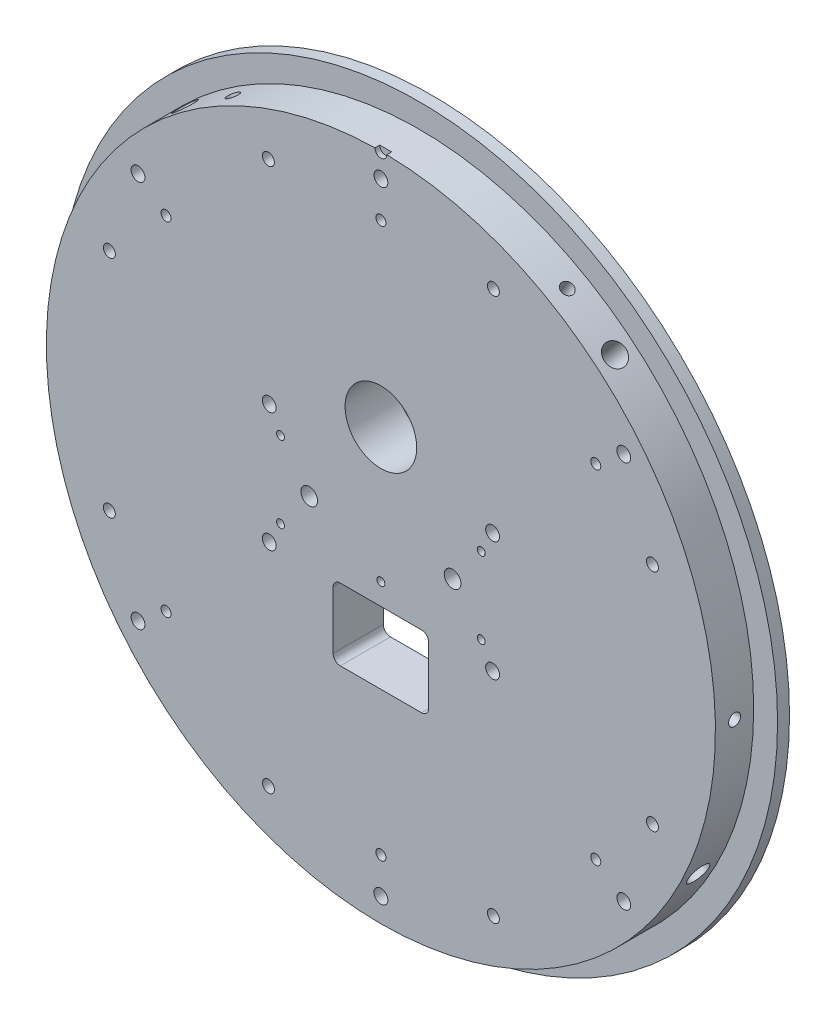
SolidWorks part; units mm, degrees
material "2017-T4"
ref_plane "正面" through (0, 0, 0) normal (0, 0, 1) x (1, 0, 0)
ref_plane "平面" through (0, 0, 0) normal (0, 1, 0) x (1, 0, 0)
ref_plane "右側面" through (0, 0, 0) normal (1, 0, 0) x (0, 0, -1)
ref_axis "中心軸" through (0, 0, -1.05) along (0, 0, 1)
sketch "ｽｹｯﾁ1" plane through (0, 0, 0) normal (0, 0, 1) x (1, 0, 0)
  circle A0 centre (0, 0) radius 150
  dimension "D1" = 300
extrude "ﾎﾞｽ - 押し出し1" add sketch "ｽｹｯﾁ1" along normal blind 5
sketch "ｽｹｯﾁ2" plane through (0, 0, 5) normal (0, 0, 1) x (1, 0, 0)
  circle A0 centre (0, 0) radius 140
  dimension "D1" = 280
extrude "ﾎﾞｽ - 押し出し2" add sketch "ｽｹｯﾁ2" along normal blind 16 contours A0
sketch "ｽｹｯﾁ3" plane through (0, 0, 0) normal (0, 0, -1) x (-1, 0, 0)
  line L1 (-20, -55) -> (20, -55)
  line L2 (-20, -55) -> (-20, -25)
  line L3 (-20, -25) -> (20, -25)
  line L4 (20, -55) -> (20, -25)
  line L5 (-20, -55) -> (20, -25) construction
  line L6 (-20, -25) -> (20, -55) construction
  circle A0 centre (0, 40) radius 15
  point P2 (0, -40)
  dimension "D1" = 30
  dimension "D2" = 40
  dimension "D3" = 40
  dimension "D4" = 30
  dimension "D5" = 55
extrude "ｶｯﾄ - 押し出し1" cut sketch "ｽｹｯﾁ3" against normal through all
fillet "ﾌｨﾚｯﾄ2" radius 3 4 edges at (20, -55, 10.5) (20, -25, 10.5) (-20, -25, 10.5) (-20, -55, 10.5)
sketch "ｽｹｯﾁ5" plane through (0, 0, 0) normal (0, 0, -1) x (-1, 0, 0)
  circle A0 centre (0, 0) radius 130
  point P3 (0, 130)
  point P4 (101.6401, 81.0511)
  point P5 (-101.6401, 81.0511)
  point P6 (-101.6401, -81.0511)
  point P7 (101.6401, -81.0511)
  point P8 (0, -130)
  dimension "D1" = 260
  dimension "D2" = 51.43
  dimension "D3" = 51.43
  dimension "D4" = 51.43
  dimension "D5" = 51.43
hole_wizard "M5 穴付きねじ用座ぐり穴1" positions "3Dｽｹｯﾁ1" profile "ｽｹｯﾁ4" counterbore size "M5" standard "JIS" end condition through all
sketch3d "3Dｽｹｯﾁ1"
  point P0 (0, 130, 0)
  point P2 (-101.6401, 81.0511, 0)
  point P4 (101.6401, 81.0511, 0)
  point P6 (101.6401, -81.0511, 0)
  point P8 (0, -130, 0)
  point P10 (-101.6401, -81.0511, 0)
sketch "ｽｹｯﾁ4" plane through (0, 130, 0) normal (1, 0, 0) x (0, 1, 0)
  line L0 (0, 0) -> (0, 21)
  line L1 (0, 21) -> (2.9, 21)
  line L3 (2.9, 21) -> (2.9, 8)
  line L4 (2.9, 8) -> (5, 8)
  line L5 (5, 8) -> (5, 0)
  line L7 (5, 0) -> (0, 0)
  line L11 (0, -6.35) -> (0, 107.95) construction
  dimension "通し穴の直径" = 5.8
  dimension "通し穴の深さ" = 21
  dimension "座ぐり穴の直径" = 10
  dimension "座ぐり穴の深さ" = 8
sketch "ｽｹｯﾁ7" plane through (0, 0, 0) normal (0, 0, -1) x (-1, 0, 0)
  point P0 (-30, 0)
  point P1 (30, 0)
  dimension "D1" = 30
  dimension "D2" = 30
hole_wizard "M6 穴付きねじ用座ぐり穴1" positions "3Dｽｹｯﾁ2" profile "ｽｹｯﾁ6" counterbore size "M6" standard "JIS" end condition through all
sketch3d "3Dｽｹｯﾁ2"
  point P0 (30, 0, 0)
  point P2 (-30, 0, 0)
sketch "ｽｹｯﾁ6" plane through (30, 0, 0) normal (1, 0, 0) x (0, 1, 0)
  line L0 (0, 0) -> (0, 21)
  line L1 (0, 21) -> (3.5, 21)
  line L3 (3.5, 21) -> (3.5, 9)
  line L4 (3.5, 9) -> (5.5, 9)
  line L5 (5.5, 9) -> (5.5, 0)
  line L7 (5.5, 0) -> (0, 0)
  line L11 (0, -6.35) -> (0, 107.95) construction
  dimension "通し穴の直径" = 7
  dimension "通し穴の深さ" = 21
  dimension "座ぐり穴の直径" = 11
  dimension "座ぐり穴の深さ" = 9
sketch "ｽｹｯﾁ8" plane through (0, 0, 0) normal (0, 0, -1) x (-1, 0, 0)
  line L1 (-46.7333, -25) -> (46.7333, -25) construction
  line L2 (-46.7333, -25) -> (-46.7333, 25) construction
  line L3 (-46.7333, 25) -> (46.7333, 25) construction
  line L4 (46.7333, -25) -> (46.7333, 25) construction
  line L5 (-46.7333, -25) -> (46.7333, 25) construction
  line L6 (-46.7333, 25) -> (46.7333, -25) construction
  point P0 (0, 0)
  dimension "D1" = 50
  dimension "D2" = 53
hole_wizard "M5 穴付きねじ用座ぐり穴2" positions "3Dｽｹｯﾁ3" profile "ｽｹｯﾁ9" counterbore size "M5" standard "JIS" end condition through all
sketch3d "3Dｽｹｯﾁ3"
  point P0 (46.7333, 25, 0)
  point P3 (46.7333, -25, 0)
  point P6 (-46.7333, 25, 0)
  point P9 (-46.7333, -25, 0)
sketch "ｽｹｯﾁ9" plane through (46.7333, 25, 0) normal (1, 0, 0) x (0, 1, 0)
  line L0 (0, 0) -> (0, 21)
  line L1 (0, 21) -> (2.9, 21)
  line L3 (2.9, 21) -> (2.9, 8)
  line L4 (2.9, 8) -> (5, 8)
  line L5 (5, 8) -> (5, 0)
  line L7 (5, 0) -> (0, 0)
  line L11 (0, -6.35) -> (0, 107.95) construction
  dimension "通し穴の直径" = 5.8
  dimension "通し穴の深さ" = 21
  dimension "座ぐり穴の直径" = 10
  dimension "座ぐり穴の深さ" = 8
sketch "ｽｹｯﾁ10" plane through (0, 0, 0) normal (0, 0, -1) x (-1, 0, 0)
  line L1 (-42, -16) -> (42, -16)
  line L2 (-42, -16) -> (-42, 16)
  line L3 (-42, 16) -> (42, 16)
  line L4 (42, -16) -> (42, 16)
  line L5 (-42, -16) -> (42, 16) construction
  line L6 (-42, 16) -> (42, -16) construction
  point P0 (0, 0)
  point P5 (0, -16)
  dimension "D1" = 84
  dimension "D2" = 32
hole_wizard "M4x0.7 ねじ穴1" positions "3Dｽｹｯﾁ4" profile "ｽｹｯﾁ11" tap size "M4x0.7" standard "JIS" end condition through all
sketch3d "3Dｽｹｯﾁ4"
  point P0 (42, 16, 0)
  point P3 (-42, 16, 0)
  point P6 (-42, -16, 0)
  point P9 (0, -16, 0)
  point P12 (42, -16, 0)
sketch "ｽｹｯﾁ11" plane through (42, 16, 0) normal (1, 0, 0) x (0, 1, 0)
  line L0 (0, 0) -> (0, 21)
  line L1 (0, 21) -> (1.65, 21)
  line L2 (1.65, 21) -> (1.65, 0)
  line L5 (1.65, 0) -> (0, 0)
  line L11 (0, -6.35) -> (0, 107.95) construction
  dimension "次ｻｰﾌｪｽまでのねじ下穴ﾄﾞﾘﾙ直径" = 3.3
  dimension "次ｻｰﾌｪｽまでのねじ下穴ﾄﾞﾘﾙの深さ" = 21
cosmetic thread "穴のねじ山1" parameters "D2"=4
cosmetic thread "穴のねじ山2" parameters "D2"=4
cosmetic thread "穴のねじ山3" parameters "D2"=4
cosmetic thread "穴のねじ山4" parameters "D2"=4
cosmetic thread "穴のねじ山5" parameters "D2"=4
sketch "ｽｹｯﾁ12" plane through (0, 0, 0) normal (0, 0, -1) x (-1, 0, 0)
  line L0 (0, 0) -> (212.6109, 0) construction
  line L1 (0, 0) -> (198.3068, 82.1414) construction
  point P3 (113.6372, 47.0701)
  dimension "D1" = 123
  dimension "D2" = 22.5
hole_wizard "M6x1.0 ねじ穴1" positions "3Dｽｹｯﾁ5" profile "ｽｹｯﾁ13" tap size "M6x1.0" standard "JIS" end condition through all
sketch3d "3Dｽｹｯﾁ5"
  point P0 (-113.6372, 47.0701, 0)
sketch "ｽｹｯﾁ13" plane through (-113.6372, 47.0701, 0) normal (1, 0, 0) x (0, 1, 0)
  line L0 (0, 0) -> (0, 21)
  line L1 (0, 21) -> (2.5, 21)
  line L2 (2.5, 21) -> (2.5, 0)
  line L5 (2.5, 0) -> (0, 0)
  line L11 (0, -6.35) -> (0, 107.95) construction
  dimension "次ｻｰﾌｪｽまでのねじ下穴ﾄﾞﾘﾙ直径" = 5
  dimension "次ｻｰﾌｪｽまでのねじ下穴ﾄﾞﾘﾙの深さ" = 21
cosmetic thread "穴のねじ山6" parameters "D2"=6
pattern_circular "円形ﾊﾟﾀｰﾝ1" count 8 over 360 about axis through (0, 0, -1.05) along (0, 0, 1) of "M6x1.0 ねじ穴1"
sketch "ｽｹｯﾁ14" plane through (0, 0, 21) normal (0, 0, -1) x (-1, 0, 0)
  circle A0 centre (0, 140) radius 2.5
  circle A2 centre (0, 0) radius 140 construction
  dimension "D1" = 5
extrude "ｶｯﾄ - 押し出し2" cut sketch "ｽｹｯﾁ14" along normal blind 2
sketch "ｽｹｯﾁ16" plane through (0, 0, 0) normal (0, 0, 1) x (1, 0, 0)
  circle A0 centre (0, 0) radius 115
  point P3 (0, 115)
  point P4 (89.9124, 71.6991)
  point P5 (-89.9124, 71.6991)
  point P6 (-89.9124, -71.6991)
  point P7 (89.9124, -71.6991)
  point P8 (0, -115)
  dimension "D1" = 230
  dimension "D2" = 51.43
  dimension "D3" = 51.43
  dimension "D4" = 51.43
  dimension "D5" = 51.43
hole_wizard "M5x0.8 ねじ穴1" positions "3Dｽｹｯﾁ6" profile "ｽｹｯﾁ17" tap size "M5x0.8" standard "JIS" end condition through all
sketch3d "3Dｽｹｯﾁ6"
  point P0 (-89.9124, 71.6991, 0)
  point P3 (-89.9124, 71.6991, 0)
  point P5 (-89.9124, -71.6991, 0)
  point P7 (0, -115, 0)
  point P9 (89.9124, -71.6991, 0)
  point P11 (89.9124, 71.6991, 0)
  point P13 (0, 115, 0)
sketch "ｽｹｯﾁ17" plane through (-89.9124, 71.6991, 0) normal (1, 0, 0) x (0, 1, 0)
  line L0 (0, 0) -> (0, 21)
  line L1 (0, 21) -> (2.1, 21)
  line L2 (2.1, 21) -> (2.1, 0)
  line L5 (2.1, 0) -> (0, 0)
  line L11 (0, -6.35) -> (0, 107.95) construction
  dimension "次ｻｰﾌｪｽまでのねじ下穴ﾄﾞﾘﾙ直径" = 4.2
  dimension "次ｻｰﾌｪｽまでのねじ下穴ﾄﾞﾘﾙの深さ" = 21
cosmetic thread "穴のねじ山7" parameters "D2"=5
cosmetic thread "穴のねじ山8" parameters "D2"=5
cosmetic thread "穴のねじ山9" parameters "D2"=5
cosmetic thread "穴のねじ山10" parameters "D2"=5
cosmetic thread "穴のねじ山11" parameters "D2"=5
cosmetic thread "穴のねじ山12" parameters "D2"=5
cosmetic thread "穴のねじ山13" parameters "D2"=5
ref_plane "平面1" through (0, 0, 13) normal (0, 0, 1) x (1, 0, 0)
sketch "ｽｹｯﾁ18" plane through (0, 0, 13) normal (0, 0, 1) x (1, 0, 0)
  circle A0 centre (0, 0) radius 140 construction
  circle A1 centre (0, 0) radius 140 construction
  point P0 (140, 0)
hole_wizard "M6x1.0 ねじ穴2" positions "3Dｽｹｯﾁ7" profile "ｽｹｯﾁ19" tap size "M6x1.0" standard "JIS"
sketch3d "3Dｽｹｯﾁ7"
  point P0 (140, 0, 13)
sketch "ｽｹｯﾁ19" plane through (140, 0, 13) normal (0, 1, 0) x (0, 0, -1)
  line L0 (0, 0) -> (0, 21.5022)
  line L1 (0, 21.5022) -> (2.5, 20)
  line L2 (2.5, 20) -> (2.5, 0)
  line L5 (2.5, 0) -> (0, 0)
  line L10 (0, 21.5022) -> (-2.5, 20) construction
  line L11 (0, -6.35) -> (0, 107.95) construction
  dimension "ねじ下穴ﾄﾞﾘﾙ直径" = 5
  dimension "ねじ下穴ﾄﾞﾘﾙの深さ" = 20
  dimension "ﾄﾞﾘﾙ角度" = 118
cosmetic thread "穴のねじ山14" parameters "D1"=12, "D2"=6
pattern_circular "円形ﾊﾟﾀｰﾝ2" count 6 over 360 about axis through (0, 0, -1.05) along (0, 0, 1) of "M6x1.0 ねじ穴2"
ref_plane "平面2" through (0, 0, 13) normal (0, 0, 1) x (1, 0, 0)
sketch "ｽｹｯﾁ20" plane through (0, 0, 13) normal (0, 0, 1) x (1, 0, 0)
  line L0 (0, 226.563) -> (0, -239.4482) construction
  line L1 (0, 0) -> (-89.9903, 107.2462) construction
  line L2 (0, 0) -> (89.9903, 107.2462) construction
  line L3 (0, 0) -> (124.7409, -63.5587) construction
  line L4 (0, 0) -> (-89.9903, -107.2462) construction
  circle A0 centre (0, 0) radius 140 construction
  arc A1 (-2.4999, 139.9777) -> (2.4999, 139.9777) centre (0, 0) ccw construction
  dimension "D1" = 40
  dimension "D2" = 40
  dimension "D3" = 63
  dimension "D4" = 40
hole_wizard "M10x1.0 ねじ穴1" positions "3Dｽｹｯﾁ8" profile "ｽｹｯﾁ21" tap size "M10x1.0" standard "JIS"
sketch3d "3Dｽｹｯﾁ8"
  point P0 (-89.9903, 107.2462, 13)
  point P2 (89.9903, 107.2462, 13)
  point P4 (124.7409, -63.5587, 13)
  point P6 (-89.9903, -107.2462, 13)
sketch "ｽｹｯﾁ21" plane through (-89.9903, 107.2462, 13) normal (0, 0, 1) x (-0.766, -0.6428, 0)
  line L0 (0, 0) -> (0, 27.7039)
  line L1 (0, 27.7039) -> (4.5, 25)
  line L2 (4.5, 25) -> (4.5, 0)
  line L5 (4.5, 0) -> (0, 0)
  line L10 (0, 27.7039) -> (-4.5, 25) construction
  line L11 (0, -6.35) -> (0, 107.95) construction
  dimension "ねじ下穴ﾄﾞﾘﾙ直径" = 9
  dimension "ねじ下穴ﾄﾞﾘﾙの深さ" = 25
  dimension "ﾄﾞﾘﾙ角度" = 118
cosmetic thread "穴のねじ山15" parameters "D1"=20, "D2"=10
cosmetic thread "穴のねじ山16" parameters "D1"=20, "D2"=10
cosmetic thread "穴のねじ山17" parameters "D1"=20, "D2"=10
cosmetic thread "穴のねじ山18" parameters "D1"=20, "D2"=10
